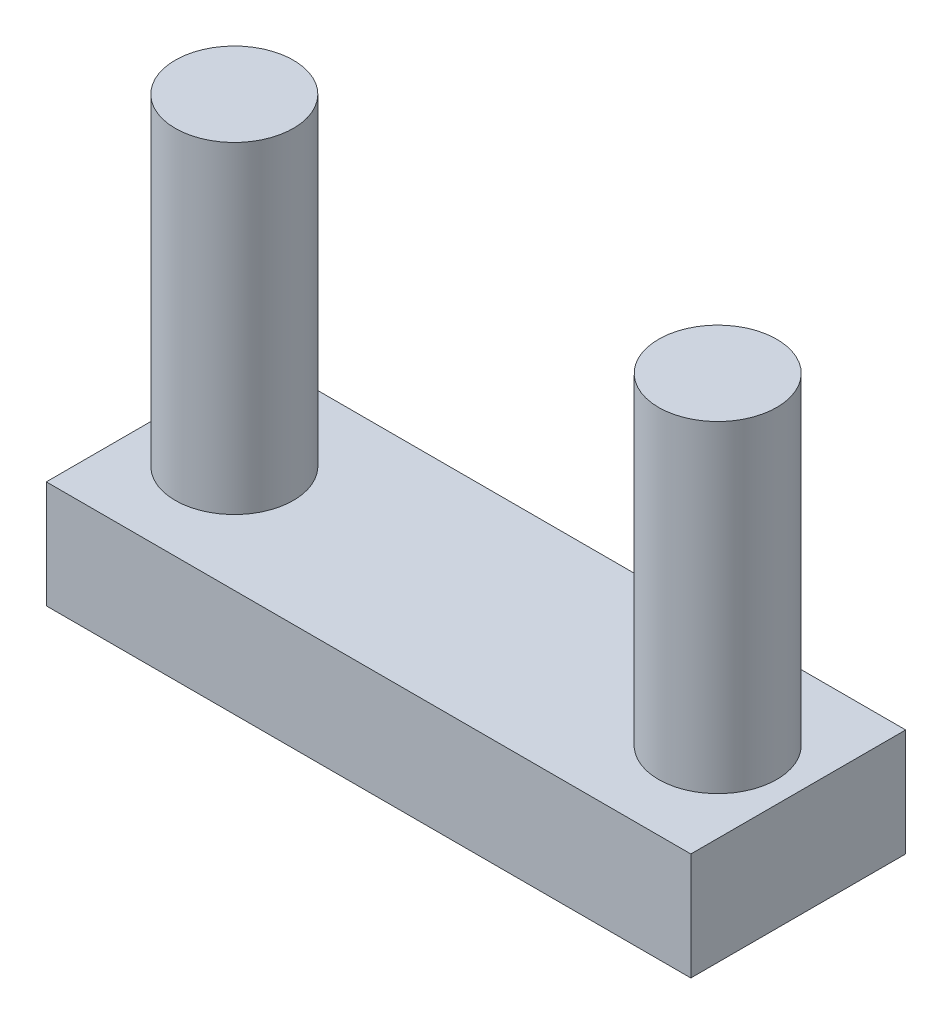
SolidWorks part; units mm, degrees
ref_plane "Front Plane" through (0, 0, 0) normal (0, 0, 1) x (1, 0, 0)
ref_plane "Top Plane" through (0, 0, 0) normal (0, 1, 0) x (1, 0, 0)
ref_plane "Right Plane" through (0, 0, 0) normal (1, 0, 0) x (0, 0, -1)
sketch "Sketch1" plane through (0, 0, 0) normal (0, 1, 0) x (1, 0, 0)
  line L0 (0, 0) -> (22.5, 0) construction
  line L2 (-3.75, 5) -> (26.25, 5)
  line L3 (-3.75, 5) -> (-3.75, -5)
  line L4 (-3.75, -5) -> (26.25, -5)
  line L5 (26.25, 5) -> (26.25, -5)
  circle A0 centre (0, 0) radius 2.75
  circle A1 centre (22.5, 0) radius 2.75
  dimension "D2" = 5.5
  dimension "D3" = 30
  dimension "D1" = 22.5
  dimension "D4" = 3.75
  dimension "D5" = 10
extrude "Boss-Extrude1" add sketch "Sketch1" along normal blind 5
extrude "Boss-Extrude2" add sketch "Sketch1<2>" along normal blind 20 contours A0 | A1 region at (0, 0, 0) region at (22.5, 0, 0)
sketch "Sketch1<2>" plane through (0, 0, 0) normal (0, 1, 0) x (1, 0, 0) same geometry as "Sketch1"
